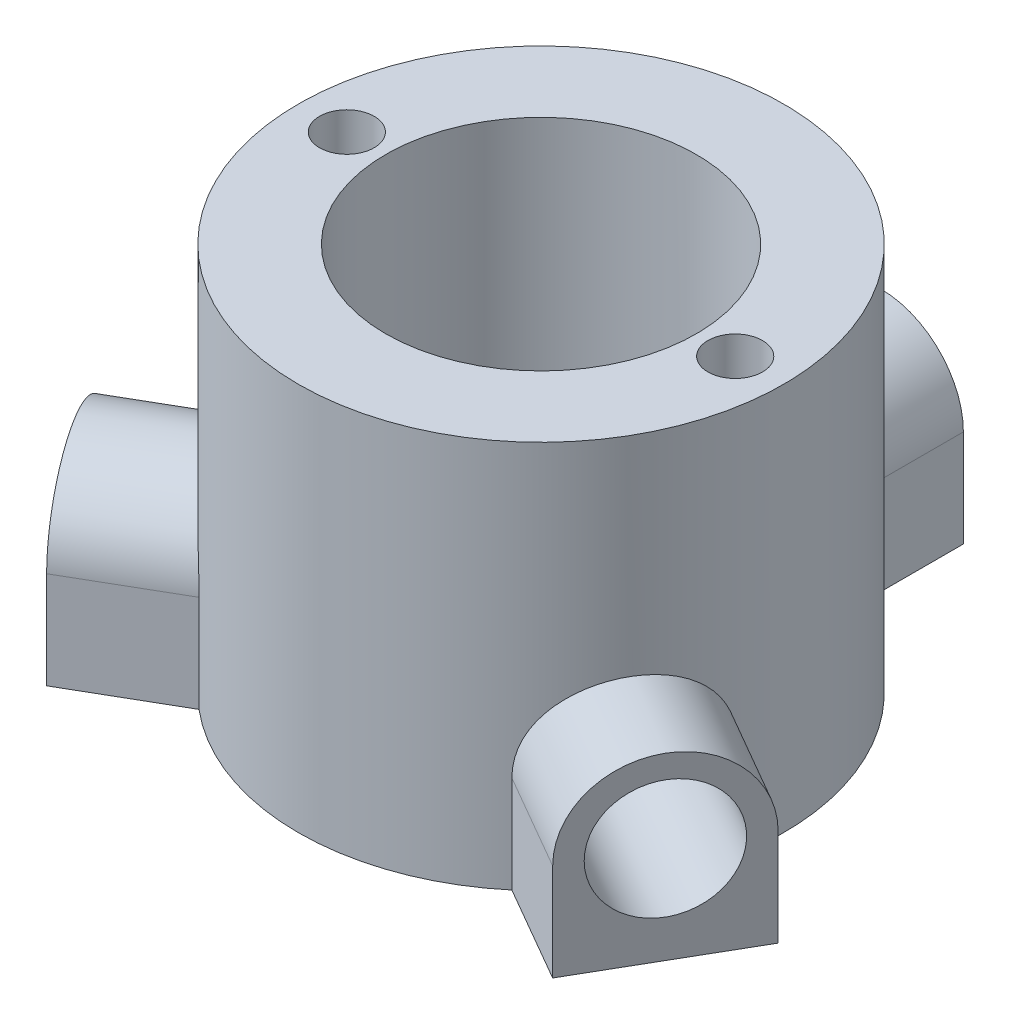
SolidWorks part; units mm, degrees
ref_plane "Front Plane" through (0, 0, 0) normal (0, 0, 1) x (1, 0, 0)
ref_plane "Top Plane" through (0, 0, 0) normal (0, 1, 0) x (1, 0, 0)
ref_plane "Right Plane" through (0, 0, 0) normal (1, 0, 0) x (0, 0, -1)
sketch "Sketch1" plane through (0, 0, 0) normal (0, 1, 0) x (1, 0, 0)
  line L0 (-25.4, 0) -> (25.4, 0) construction
  circle A0 centre (0, 0) radius 31.75
  circle A1 centre (0, 0) radius 20.32
  point P5 (0, 0)
  dimension "D1" = 63.5
  dimension "D3" = 40.64
  dimension "D2" = 50.8
extrude "Boss-Extrude1" add sketch "Sketch1" along normal blind 50.8
ref_plane "Plane1" through (0, 0, -31.75) normal (0, 0, 1) x (1, 0, 0)
sketch "Sketch2" plane through (0, 0, -31.75) normal (0, 0, 1) x (1, 0, 0)
  line L0 (-31.75, 0) -> (31.75, 0) construction
  line L1 (10.795, 12.7) -> (10.795, 0)
  line L2 (-10.795, 12.7) -> (-10.795, 0)
  line L3 (-10.795, 0) -> (10.795, 0)
  circle A0 centre (0, 12.7) radius 7.7788
  arc A1 (10.795, 12.7) -> (-10.795, 12.7) centre (0, 12.7) ccw
  dimension "D1" = 15.5575
  dimension "D2" = 21.59
  dimension "D3" = 12.7
extrude "Boss-Extrude2" add sketch "Sketch2" against normal blind 12.7 and the other way up to surface other way up to face at (0, 50.8, 31.75)
extrude "Cut-Extrude1" cut sketch "Sketch2<2>" along normal up to surface (12.9779 mm away) contours A0 region at (0, 12.7, -31.75) up to face at (0, 50.8, 20.32)
sketch "Sketch2<2>" plane through (0, 0, -31.75) normal (0, 0, 1) x (1, 0, 0) same geometry as "Sketch2"
pattern_circular "CirPattern1" count 3 every 120 about axis through (0, 50.8, 0) along (0, -1, 0) of "Boss-Extrude2", "Cut-Extrude1"
sketch "Sketch3" plane through (0, 50.8, 0) normal (0, 1, 0) x (1, 0, 0)
  point P0 (-25.4, 0)
  point P3 (25.4, 0)
hole_wizard "1/4 Clearance Hole1" positions "Sketch3" profile "Sketch4" hole size "1/4" standard "ANSI Inch" end condition through all
sketch "Sketch4" plane through (-25.4, 50.8, 0) normal (1, 0, 0) x (0, 0, 1)
  line L0 (0, 0) -> (0, 50.8)
  line L1 (0, 50.8) -> (3.5712, 50.8)
  line L2 (3.5712, 50.8) -> (3.5712, 0)
  line L5 (3.5712, 0) -> (0, 0)
  line L11 (0, -6.35) -> (0, 107.95) construction
  dimension "Thru Hole Dia." = 7.1425
  dimension "Thru Hole Depth" = 50.8
